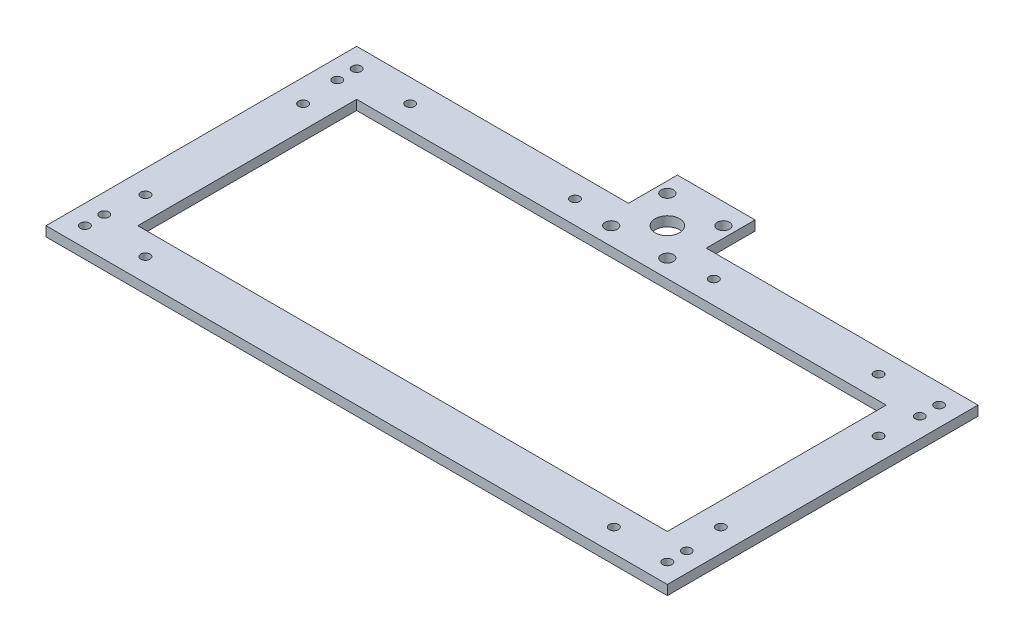
SolidWorks part; units mm, degrees
ref_plane "Front" through (0, 0, 0) normal (0, 0, 1) x (1, 0, 0)
ref_plane "Top" through (0, 0, 0) normal (0, 1, 0) x (1, 0, 0)
ref_plane "Right" through (0, 0, 0) normal (1, 0, 0) x (0, 0, -1)
sketch "Sketch1" plane through (0, 0, 0) normal (0, 1, 0) x (1, 0, 0)
  line L0 (6.35, 101.6) -> (6.35, 95.25)
  line L1 (0, 0) -> (203.2, 0)
  line L2 (0, 0) -> (0, 101.6)
  line L3 (0, 101.6) -> (203.2, 101.6)
  line L4 (203.2, 0) -> (203.2, 101.6)
  line L5 (15, 86.6) -> (188.2, 86.6)
  line L6 (15, 86.6) -> (15, 15)
  line L7 (15, 15) -> (188.2, 15)
  line L8 (188.2, 86.6) -> (188.2, 15)
  line L9 (6.35, 95.25) -> (6.35, 88.9)
  line L10 (15, 50.8) -> (2.3, 50.8)
  line L11 (101.6, 15) -> (101.6, 2.3)
  line L12 (101.6, 101.6) -> (101.6, 117.6)
  line L13 (88.9, 101.6) -> (114.3, 101.6)
  line L14 (88.9, 101.6) -> (88.9, 203.2)
  line L15 (88.9, 203.2) -> (114.3, 203.2)
  line L16 (114.3, 101.6) -> (114.3, 203.2)
  line L17 (101.6, 117.6) -> (114.3, 117.6)
  line L18 (114.3, 117.6) -> (88.9, 117.6)
  circle A0 centre (6.35, 95.25) radius 1.5
  circle A1 centre (6.35, 88.9) radius 1.5
  circle A2 centre (6.35, 6.35) radius 1.5
  circle A3 centre (6.35, 12.7) radius 1.5
  circle A4 centre (196.85, 95.25) radius 1.5
  circle A5 centre (196.85, 88.9) radius 1.5
  circle A6 centre (196.85, 12.7) radius 1.5
  circle A7 centre (196.85, 6.35) radius 1.5
  dimension "D10" = 25.4
  dimension "D1" = 101.6
  dimension "D2" = 203.2
  dimension "D3" = 15
  dimension "D4" = 15
  dimension "D5" = 15
  dimension "D6" = 15
  dimension "D7" = 6.35
  dimension "D8" = 6.35
  dimension "D9" = 6.35
  dimension "D11" = 101.6
  dimension "D12" = 88.9
  dimension "D13" = 16
extrude "Boss-Extrude1" add sketch "Sketch1" along normal blind 3.175 contours A1 A0 L3 L2 L10 L6 L5 L8 L7 L11 L1 L4 A7 A6 A4 A5 | L11 L7 L6 L10 L2 L1 A2 A3 | L17 L12 L3 L16 | L12 L18 L14 L3 region at (47.625, 0, -99.3282) region at (95.25, 0, -109.6) region at (107.95, 0, -109.6)
sketch "Sketch2" plane through (0, 3.175, 0) normal (0, 1, 0) x (1, 0, 0)
  line L0 (88.9, 101.6) -> (114.3, 101.6)
  line L1 (92.4231, 92.4231) -> (110.7769, 110.7769)
  line L2 (92.4231, 110.7769) -> (110.7769, 92.4231)
  circle A0 centre (101.6, 101.6) radius 12.9781
  circle A1 centre (92.4231, 110.7769) radius 2
  circle A2 centre (110.7769, 110.7769) radius 2
  circle A3 centre (92.4231, 92.4231) radius 2
  circle A4 centre (110.7769, 92.4231) radius 2
  circle A5 centre (101.6, 101.6) radius 4
  point P9 (101.6, 101.6)
  point P12 (101.6, 101.6)
extrude "Cut-Extrude1" cut sketch "Sketch2" against normal blind 3.175 contours A0 A2 | L1 A2 A0 | A0 A2 L1 | A1 | A3 | A4 | A5 region at (109.5728, 3.175, -110.7421) region at (110.7421, 3.175, -109.5728) region at (111.3571, 3.175, -111.3571)
sketch "Sketch3" plane through (0, 3.175, 0) normal (0, 1, 0) x (1, 0, 0)
  line L0 (188.2, 86.6) -> (188.2, 101.6)
  line L1 (114.3, 101.6) -> (203.2, 101.6) construction
  line L2 (188.2, 101.6) -> (188.2, 86.6)
  line L3 (203.2, 86.6) -> (188.2, 86.6)
  line L4 (203.2, 0) -> (203.2, 101.6) construction
  line L5 (188.2, 15) -> (203.2, 15)
  line L6 (203.2, 15) -> (188.2, 15)
  line L7 (188.2, 0) -> (188.2, 15)
  line L8 (0, 0) -> (203.2, 0) construction
  line L9 (15, 86.6) -> (0, 86.6)
  line L10 (0, 0) -> (0, 101.6) construction
  line L11 (195.7, 86.6) -> (195.7, 15)
  line L12 (188.2, 7.5) -> (15, 7.5)
  line L13 (7.5, 86.6) -> (7.5, 15)
  line L14 (188.2, 94.1) -> (15, 94.1)
  line L15 (114.3, 101.6) -> (114.3, 117.6) construction
  line L16 (88.9, 101.6) -> (88.9, 117.6) construction
  circle A0 centre (178.2, 94.1) radius 1.5
  circle A1 centre (25, 94.1) radius 1.5
  circle A2 centre (78.9, 94.1) radius 1.5
  circle A3 centre (124.3, 94.1) radius 1.5
  circle A4 centre (178.2, 7.5) radius 1.5
  circle A5 centre (25, 7.5) radius 1.5
  circle A6 centre (195.7, 76.6) radius 1.5
  circle A8 centre (195.7, 25) radius 1.5
  circle A9 centre (7.5, 76.6) radius 1.5
  circle A10 centre (7.5, 25) radius 1.5
  dimension "D1" = 10
  dimension "D5" = 10
  dimension "D2" = 10
  dimension "D3" = 10
  dimension "D4" = 10
  dimension "D6" = 10
  dimension "D7" = 10
  dimension "D8" = 10
extrude "Cut-Extrude2" cut sketch "Sketch3" against normal blind 10 contours A0 | A3 | A2 | A1 | A9 | A5 | A10 | A4 | A8 | A6
sketch "Sketch4" plane through (0, 3.175, 0) normal (0, 1, 0) x (1, 0, 0)
  line L0 (101.6, 203.2) -> (101.6, 190.5)
  line L1 (88.9, 203.2) -> (114.3, 203.2) construction
  circle A0 centre (101.6, 190.5) radius 3.175
sketch "Sketch5" plane through (0, 3.175, 0) normal (0, 1, 0) x (1, 0, 0)
  line L0 (101.6, 101.6) -> (101.6, 127)
  line L1 (101.6, 127) -> (101.6, 177.8)
  circle A0 centre (101.6, 177.8) radius 1.5
  circle A1 centre (101.6, 127) radius 1.5
  dimension "D1" = 25.4
  dimension "D2" = 50.8
